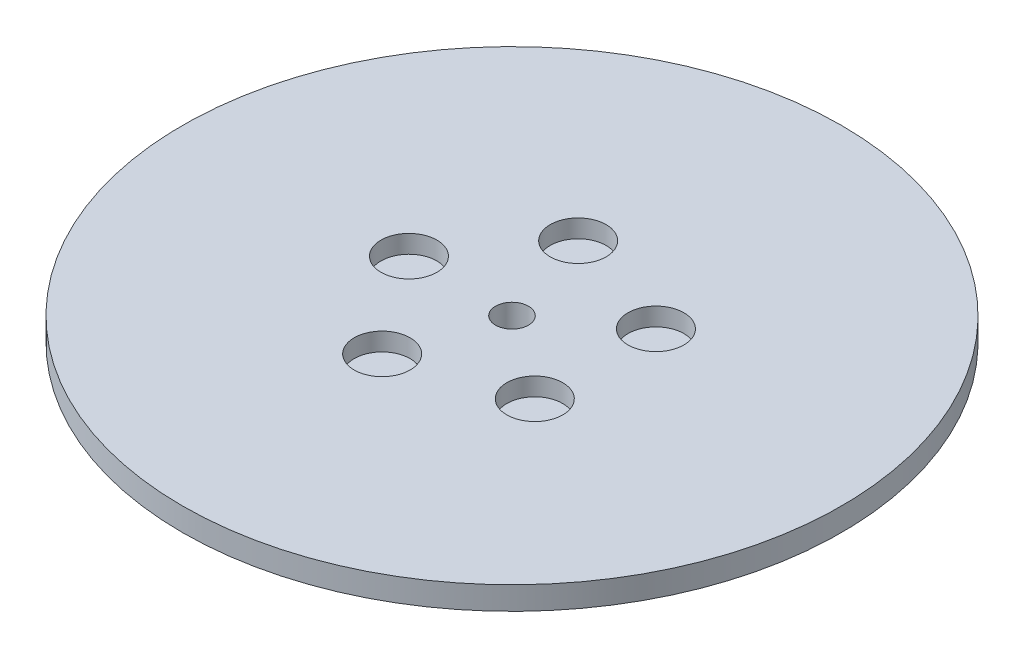
SolidWorks part; units mm, degrees
ref_plane "Front Plane" through (0, 0, 0) normal (0, 0, 1) x (1, 0, 0)
ref_plane "Top Plane" through (0, 0, 0) normal (0, 1, 0) x (1, 0, 0)
ref_plane "Right Plane" through (0, 0, 0) normal (1, 0, 0) x (0, 0, -1)
sketch "Sketch1" plane through (0, 0, 0) normal (0, 1, 0) x (1, 0, 0)
  circle A0 centre (0, 0) radius 100
  dimension "FLANGE_OD" = 200
extrude "Boss-Extrude1" add sketch "Sketch1" along normal blind 7
sketch "Sketch2" plane through (0, 0, 0) normal (0, 1, 0) x (1, 0, 0)
  circle A0 centre (0, 0) radius 5
  dimension "BORE_D" = 10
extrude "Cut-Extrude1" cut sketch "Sketch2" along normal through all
sketch "Sketch3" plane through (0, 7, 0) normal (0, 1, 0) x (1, 0, 0)
  circle A0 centre (0, 0) radius 31.2676 construction
  circle A1 centre (-31.2676, 0) radius 8.4799
  dimension "BOLT_D" = 16.9598
  dimension "BOLT_PCD" = 62.5353
extrude "Cut-Extrude2" cut sketch "Sketch3" against normal blind 5.4827
pattern_circular "CirPattern1" count 5 over 360 about axis through (0, 0, 0) along (0, 1, 0) of "Cut-Extrude2"
